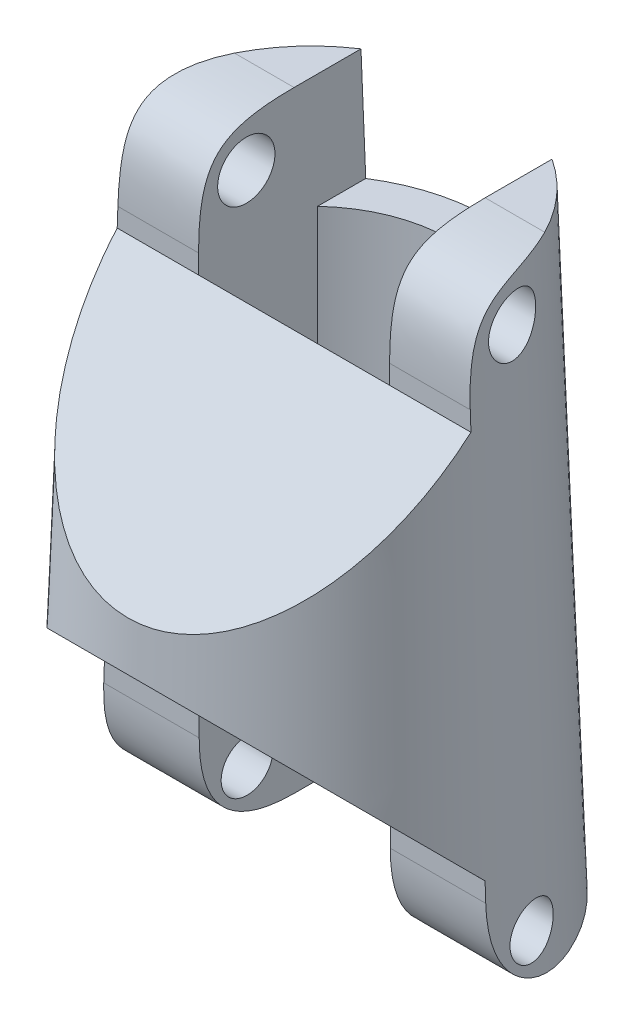
SolidWorks part; units mm, degrees
ref_plane "Front Plane" through (0, 0, 0) normal (0, 0, 1) x (1, 0, 0)
ref_plane "Top Plane" through (0, 0, 0) normal (0, 1, 0) x (1, 0, 0)
ref_plane "Right Plane" through (0, 0, 0) normal (1, 0, 0) x (0, 0, -1)
sketch "Sketch1" plane through (0, 0, 0) normal (0, 1, 0) x (1, 0, 0)
  circle A0 centre (0, 0) radius 10
  dimension "D1" = 20
extrude "Boss-Extrude1" add sketch "Sketch1" along normal blind 26 draft 2 and the other way blind 6 draft 2
sketch "Sketch2" plane through (0, 0, 0) normal (1, 0, 0) x (0, 0, -1)
  line L0 (-0.9079, 26) -> (-0.9079, 20)
  line L2 (9.0921, 26) -> (-9.0921, 26) construction
  line L3 (-0.9079, 20) -> (-13.4156, 7.4923)
  line L5 (-13.4156, 7.4923) -> (-13.4156, 26)
  line L6 (-13.4156, 26) -> (-0.9079, 26)
  dimension "D1" = 10
  dimension "D2" = 6
  dimension "D3" = 135
extrude "Cut-Extrude1" cut sketch "Sketch2" against normal through all both and the other way through all
sketch "Sketch3" plane through (0, 0, 0.9079) normal (0, 0, 1) x (1, 0, 0)
  line L0 (-9.2572, 20) -> (9.2572, 20) construction
  line L1 (5, 26) -> (-5, 26)
  line L2 (5, 26) -> (5, 20)
  line L3 (5, 20) -> (-5, 20)
  line L4 (-5, 26) -> (-5, 20)
  line L5 (5, 26) -> (-5, 20) construction
  line L6 (5, 20) -> (-5, 26) construction
  point P0 (0, 23)
  dimension "D1" = 10
  dimension "D2" = 6
extrude "Cut-Extrude2" cut sketch "Sketch3" against normal blind 25
sketch "Sketch4" plane through (-5, 0, 0) normal (1, 0, 0) x (0, 0, -1)
  circle A0 centre (1.5921, 23.5) radius 1.5
  dimension "D3" = 3
  dimension "D1" = 2.5
  dimension "D2" = 2.5
extrude "Cut-Extrude3" cut sketch "Sketch4" against normal through all both and the other way through all
fillet "Fillet2" radius 5 2 edges at (7.0233, 26, 0.9079) (-7.0233, 26, 0.9079)
sketch "Sketch7" plane through (0, 0, 0) normal (1, 0, 0) x (0, 0, -1)
  line L0 (-0.873, -6) -> (-0.873, 0)
  line L1 (-10.2095, -6) -> (10.2095, -6) construction
  line L2 (-0.873, 0) -> (-11.3178, 10.4448)
  line L3 (-11.3178, 10.4448) -> (-11.3178, -6)
  line L4 (-11.3178, -6) -> (-0.873, -6)
  dimension "D1" = 6
  dimension "D2" = 135
extrude "Cut-Extrude5" cut sketch "Sketch7" against normal through all both and the other way through all
sketch "Sketch8" plane through (0, 0, 0.873) normal (0, 0, 1) x (1, 0, 0)
  line L0 (-9.9618, 0) -> (9.9618, 0) construction
  line L1 (-5, -6) -> (5, -6)
  line L2 (-5, -6) -> (-5, 0)
  line L3 (-5, 0) -> (5, 0)
  line L4 (5, -6) -> (5, 0)
  line L5 (-5, -6) -> (5, 0) construction
  line L6 (-5, 0) -> (5, -6) construction
  point P0 (0, -3)
  dimension "D1" = 6
  dimension "D2" = 10
  dimension "D3" = 0
extrude "Cut-Extrude6" cut sketch "Sketch8" against normal through all
sketch "Sketch6" plane through (0, 20, 0) normal (0, 1, 0) x (1, 0, 0)
  line L0 (5, 7.8434) -> (5, -0.9079) construction
  line L1 (-5, -0.9079) -> (5, -0.9079) construction
  line L2 (-5, 7.8434) -> (-5, -0.9079) construction
  line L3 (5, 5.321) -> (5, -0.9079)
  line L4 (-5, -0.9079) -> (5, -0.9079)
  line L5 (-5, 5.321) -> (-5, -0.9079)
  arc A3 (3.9249, 6.157) -> (-3.9249, 6.157) centre (0, 0) ccw
  arc A4 (5, 5.321) -> (-5, 5.321) centre (0, 0) ccw
  dimension "D1" = 2
extrude "Cut-Extrude7" cut sketch "Sketch6" against normal through all contours A4 L5 L4 L3
sketch "Sketch9" plane through (-5, 0, 0) normal (1, 0, 0) x (0, 0, -1)
  circle A0 centre (1.627, -3.5) radius 1.3515
  dimension "D1" = 2.5
  dimension "D2" = 2.5
extrude "Cut-Extrude8" cut sketch "Sketch9" against normal through all both and the other way through all
fillet "Fillet3" radius 5 2 edges at (7.5861, -6, 0.873) (-7.5861, -6, 0.873)
